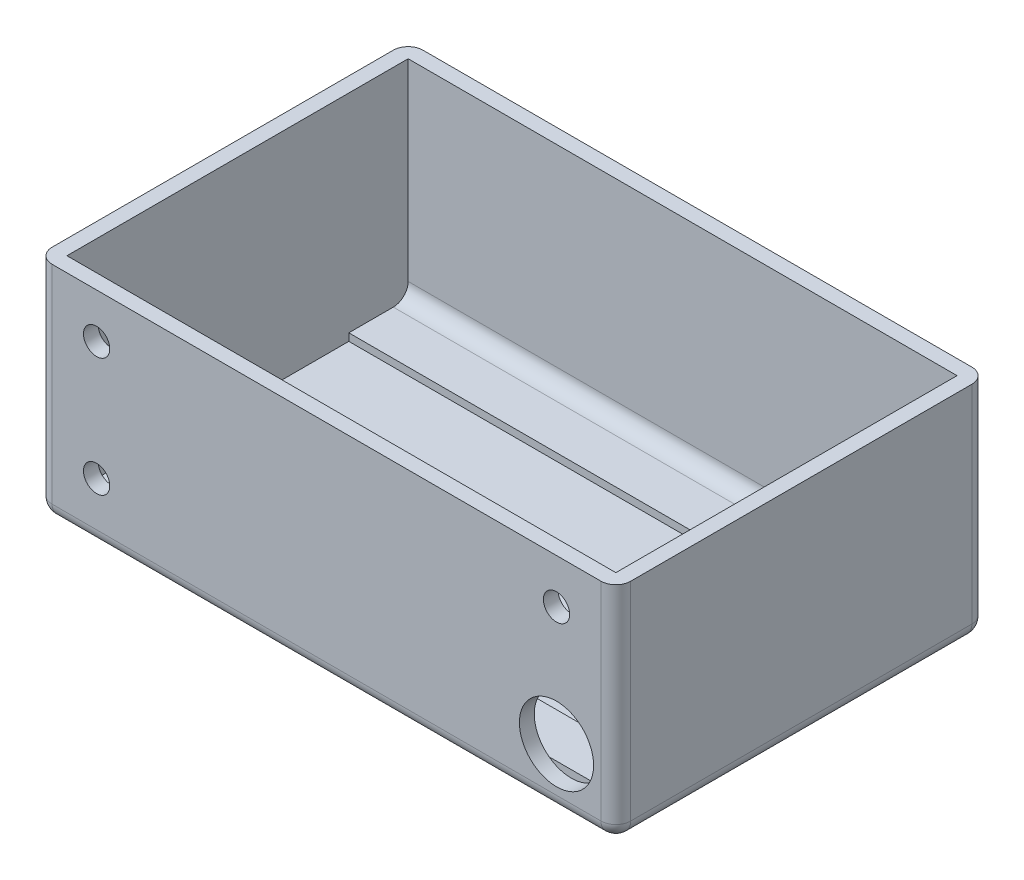
SolidWorks part; units mm, degrees
ref_plane "Front Plane" through (0, 0, 0) normal (0, 0, 1) x (1, 0, 0)
ref_plane "Top Plane" through (0, 0, 0) normal (0, 1, 0) x (1, 0, 0)
ref_plane "Right Plane" through (0, 0, 0) normal (1, 0, 0) x (0, 0, -1)
sketch "Sketch1" plane through (0, 0, 0) normal (1, 0, 0) x (0, 0, -1)
  line L0 (31.75, 0) -> (-31.75, 0)
  line L1 (-31.75, 0) -> (-31.75, 38.1)
  line L2 (-31.75, 38.1) -> (-29.21, 38.1)
  line L3 (-29.21, 38.1) -> (-29.21, 2.54)
  line L4 (-29.21, 2.54) -> (-19.05, 2.54)
  line L5 (-19.05, 2.54) -> (-19.05, 1.27)
  line L6 (-19.05, 1.27) -> (-6.35, 1.27)
  line L7 (-6.35, 1.27) -> (-6.35, 2.54)
  line L8 (-6.35, 2.54) -> (6.35, 2.54)
  line L9 (0, 2.54) -> (0, 0)
  line L10 (6.35, 1.27) -> (6.35, 2.54)
  line L11 (19.05, 1.27) -> (6.35, 1.27)
  line L12 (19.05, 2.54) -> (19.05, 1.27)
  line L13 (29.21, 2.54) -> (19.05, 2.54)
  line L14 (29.21, 38.1) -> (29.21, 2.54)
  line L15 (31.75, 38.1) -> (29.21, 38.1)
  line L16 (31.75, 0) -> (31.75, 38.1)
  dimension "D1" = 38.1
  dimension "D2" = 2.54
  dimension "D3" = 1.27
  dimension "D4" = 2.54
  dimension "D5" = 12.7
  dimension "D6" = 6.35
  dimension "D7" = 2.54
  dimension "D8" = 31.75
extrude "Boss-Extrude1" add sketch "Sketch1" along normal mid plane 96.52 contours L4 L5 L6 L7 L8 L10 L11 L12 L13 L14 L15 L16 L0 L1 L2 L3
fillet "Fillet1" radius 2.54 4 edges at (0, 0, -31.75) (0, 0, 31.75) (0, 2.54, -29.21) (0, 2.54, 29.21)
sketch "Sketch3" plane through (0, 0, 0) normal (1, 0, 0) x (0, 0, -1)
  line L0 (-31.75, 38.1) -> (-31.75, 2.54)
  line L1 (-31.75, 38.1) -> (31.75, 38.1)
  line L2 (0, 38.1) -> (0, 0)
  line L3 (29.21, 0) -> (-29.21, 0)
  line L4 (31.75, 38.1) -> (31.75, 2.54)
  arc A0 (-31.75, 2.54) -> (-29.21, 0) centre (-29.21, 2.54) ccw
  arc A1 (31.75, 2.54) -> (29.21, 0) centre (29.21, 2.54) cw
  dimension "D1" = 2.54
extrude "Boss-Extrude2" add sketch "Sketch3" along normal blind 2.54 from surface contours L0 A0 L3 L2 L1 | A1 L4 L1 L2 L3 region at (0, 19.0712, 15.8575) region at (0, 19.0712, -15.8575) starting at face at (-48.26, 9.2928, 0)
extrude "Boss-Extrude3" add sketch "Sketch3<3>" along normal blind 2.54 from surface contours A1 L4 L1 L2 L3 | L0 A0 L3 L2 L1 region at (0, 19.0712, 15.8575) region at (0, 19.0712, -15.8575) starting at face at (48.26, 9.2928, 0)
sketch "Sketch3<3>" plane through (0, 0, 0) normal (1, 0, 0) x (0, 0, -1) same geometry as "Sketch3"
sketch "Sketch4" plane through (0, 0, 0) normal (0, 0, 1) x (1, 0, 0)
  line L0 (50.8, 2.54) -> (50.8, 38.1) construction
  line L1 (50.8, 0) -> (-48.26, 0) construction
  circle A0 centre (40.64, 10.16) radius 6.35
  dimension "D1" = 12.7
  dimension "D2" = 10.16
  dimension "D3" = 10.16
extrude "Cut-Extrude2" cut sketch "Sketch4" along normal up to surface (31.75 mm away) from surface contours A0 up to face at (1.27, 20.32, 31.75) starting at face at (1.27, 21.59, 29.21)
fillet "Fillet2" radius 2.54 10 edges at (50.8, 0.7439, 31.0061) (50.8, 0, 0) (50.8, 0.7439, -31.0061) (-48.26, 0.7439, 31.0061) (-48.26, 0, 0) (-48.26, 0.7439, -31.0061) (50.8, 20.32, 31.75) (50.8, 20.32, -31.75) (-48.26, 20.32, 31.75) (-48.26, 20.32, -31.75)
hole_wizard "M4 Clearance Hole1" positions "Sketch5" profile "Sketch6" hole size "M4" standard "ISO" end condition through all
sketch "Sketch5" plane through (0, 0, 29.21) normal (0, 0, -1) x (-1, 0, 0)
  line L0 (-50.8, 38.1) -> (-50.8, 2.54) construction
  line L1 (-48.26, 38.1) -> (45.72, 38.1) construction
  line L2 (48.26, 2.54) -> (48.26, 38.1) construction
  point P0 (-40.64, 30.48)
  point P2 (38.1, 30.48)
  point P4 (38.1, 10.16)
  dimension "D1" = 10.16
  dimension "D2" = 7.62
  dimension "D3" = 10.16
  dimension "D4" = 20.32
sketch "Sketch6" plane through (40.64, 30.48, 29.21) normal (1, 0, 0) x (0, 1, 0)
  line L0 (0, 0) -> (0, 2.54)
  line L1 (0, 2.54) -> (2.25, 2.54)
  line L2 (2.25, 2.54) -> (2.25, 0)
  line L5 (2.25, 0) -> (0, 0)
  line L11 (0, -6.35) -> (0, 107.95) construction
  dimension "Thru Hole Dia." = 4.5
  dimension "Thru Hole Depth" = 2.54
